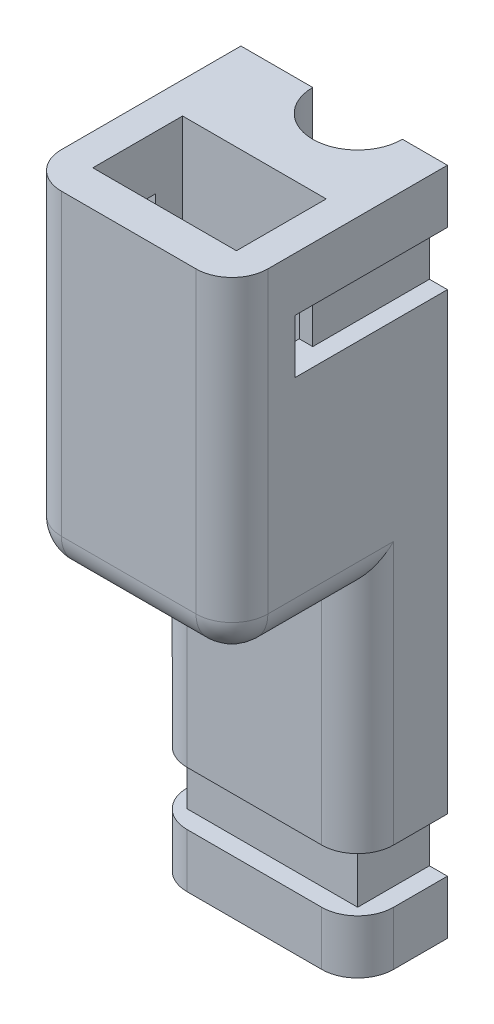
SolidWorks part; units mm, degrees
ref_plane "Alzado" through (0, 0, 0) normal (0, 0, 1) x (1, 0, 0)
ref_plane "Planta" through (0, 0, 0) normal (0, 1, 0) x (1, 0, 0)
ref_plane "Vista lateral" through (0, 0, 0) normal (1, 0, 0) x (0, 0, -1)
sketch "Croquis1" plane through (0, 0, 0) normal (0, 0, 1) x (1, 0, 0)
  line L0 (0, 7) -> (0, -7)
  line L1 (0, -7) -> (0, -10)
  line L2 (0, 0) -> (-3.5, 0) construction
  line L3 (-3.5, 7) -> (-3.5, -7)
  line L4 (-3.5, -7) -> (-2.5, -9.6451)
  line L5 (-2.5, -9.6451) -> (-2.5, -18.6451)
  line L6 (-2.5, -18.6451) -> (-0.8, -18.6451)
  line L12 (0, 7) -> (0, 10)
  line L18 (-2.5, 18.6451) -> (-0.8, 18.6451)
  line L19 (-2.5, 9.6451) -> (-2.5, 18.6451)
  line L20 (-3.5, 7) -> (-2.5, 9.6451)
  dimension "D1" = 7
  dimension "D2" = 3
  dimension "D3" = 7
  dimension "D4" = 9
  dimension "D5" = 2.5
  dimension "D6" = 3.5
  dimension "D7" = 1.7
ref_plane "Plano1" through (0, 0, 0) normal (0, 0, 1) x (1, 0, 0)
sketch "Croquis2" plane through (0, 0, 0) normal (0, 0, 1) x (1, 0, 0)
  line L0 (0, 18.6451) -> (-2.5, 18.6451)
  line L1 (-2.5, 18.6451) -> (-2.5, 9.6451)
  line L2 (-2.5, 9.6451) -> (-3.5, 7)
  line L3 (-3.5, 7) -> (-3.5, -7)
  line L4 (-3.5, -7) -> (-2.5, -9.6451)
  line L5 (-2.5, -9.6451) -> (-2.5, -18.6451)
  line L6 (-2.5, -18.6451) -> (0, -18.6451)
  line L7 (0, -18.6451) -> (0, 18.6451)
  line L9 (-6.5, 18.6451) -> (5, 18.6451)
  line L10 (-6.5, 18.6451) -> (-6.5, -18.6451)
  line L11 (-6.5, -18.6451) -> (5, -18.6451)
  line L12 (5, 18.6451) -> (5, -18.6451)
  dimension "D1" = 5
  dimension "D2" = 3
extrude "Saliente-Extruir1" add sketch "Croquis2" along normal blind 5 contours L12 L11 L10 L9
revolve "Cortar-Revolución1" cut sketch "Croquis2<4>" angle 360 about L12 region at (-1.5111, 0, 0)
sketch "Croquis2<4>" plane through (0, 0, 0) normal (0, 0, 1) x (1, 0, 0) same geometry as "Croquis2"
sketch "Croquis3" plane through (0, 0, 0) normal (0, 0, -1) x (-1, 0, 0)
  line L0 (0, 0) -> (0, 3.5)
  line L1 (0, 7) -> (0, -7) construction
  line L5 (12, 2.5) -> (0, 3.5)
  line L6 (12, 0) -> (12, 2.5)
  line L7 (0, 0) -> (12, 0)
  dimension "D1" = 3.5
revolve "Cortar-Revolución2" cut sketch "Croquis3" angle 360 about L7
sketch "Croquis6" plane through (0, 0, 5) normal (0, 0, 1) x (1, 0, 0)
  line L0 (5, 18.6451) -> (5, -18.6451) construction
  line L1 (5, 0) -> (-6.5, 0)
  line L2 (5, 0) -> (5, 18.6451)
  line L3 (5, 18.6451) -> (-6.5, 18.6451)
  line L4 (-6.5, 0) -> (-6.5, 18.6451)
extrude "Saliente-Extruir2" add sketch "Croquis6" along normal blind 7
sketch "Croquis4" plane through (0, 0, 0) normal (0, 0, -1) x (-1, 0, 0)
  line L0 (-5, 18.6451) -> (-5, -18.6451) construction
  line L1 (-5, 15.6451) -> (-4, 15.6451)
  line L2 (-5, 15.6451) -> (-5, 12.6451)
  line L3 (-5, 12.6451) -> (-4, 12.6451)
  line L4 (-4, 15.6451) -> (-4, 12.6451)
  line L5 (-2.5, 18.6451) -> (-5, 18.6451) construction
  line L6 (5.5, 15.6451) -> (6.5, 15.6451)
  line L7 (5.5, 15.6451) -> (5.5, 12.6451)
  line L8 (5.5, 12.6451) -> (6.5, 12.6451)
  line L9 (6.5, 15.6451) -> (6.5, 12.6451)
  line L10 (5.5, -12.6451) -> (6.5, -12.6451)
  line L11 (5.5, -12.6451) -> (5.5, -15.6451)
  line L12 (5.5, -15.6451) -> (6.5, -15.6451)
  line L13 (6.5, -12.6451) -> (6.5, -15.6451)
  line L14 (-5, -12.6451) -> (-4, -12.6451)
  line L15 (-5, -12.6451) -> (-5, -15.6451)
  line L16 (-5, -15.6451) -> (-4, -15.6451)
  line L17 (-4, -12.6451) -> (-4, -15.6451)
  line L18 (-2.5, -18.6451) -> (-5, -18.6451) construction
  line L19 (6.5, 18.6451) -> (6.5, 2.9583) construction
  dimension "D1" = 1
  dimension "D2" = 3
  dimension "D3" = 3
  dimension "D6" = 3
  dimension "D7" = 0
  dimension "D4" = 2
  dimension "D5" = 2
extrude "Cortar-Extruir2" cut sketch "Croquis4" against normal blind 6.5
sketch "Croquis5" plane through (4, 0, 0) normal (1, 0, 0) x (0, 0, -1)
  line L0 (-6.5, 15.6451) -> (0, 15.6451) construction
  line L1 (-8.5, 12.6451) -> (-6.5, 12.6451)
  line L2 (-8.5, 12.6451) -> (-8.5, 15.6451)
  line L3 (-8.5, 15.6451) -> (-6.5, 15.6451)
  line L4 (-6.5, 12.6451) -> (-6.5, 15.6451)
  line L5 (-5, -15.6451) -> (-5, -12.6451) construction
  line L6 (-7.9583, -12.6451) -> (-7.9583, -15.6451)
  line L7 (-4, -15.6451) -> (-7.9583, -15.6451)
  line L8 (-4, -12.6451) -> (-4, -15.6451)
  line L9 (-4, -12.6451) -> (-7.9583, -12.6451)
  line L10 (0, 12.6451) -> (0, 15.6451) construction
  dimension "D1" = 2
  dimension "D2" = 6.5
  dimension "D3" = 1
extrude "Cortar-Extruir3" cut sketch "Croquis5" against normal up to vertex (10.5 mm away) and the other way up to vertex (1 mm away) up to point (-6.5, 18.6451, 12) other way up to point (5, 18.6451, 12)
sketch "Croquis7" plane through (0, 18.6451, 0) normal (0, 1, 0) x (1, 0, 0)
  line L0 (5, -12) -> (-6.5, -12) construction
  line L1 (3.25, -10) -> (-4.75, -10)
  line L2 (3.25, -10) -> (3.25, -5)
  line L3 (3.25, -5) -> (-4.75, -5)
  line L4 (-4.75, -10) -> (-4.75, -5)
  line L5 (-6.5, -12) -> (-6.5, 0) construction
  dimension "D1" = 8
  dimension "D2" = 5
  dimension "D3" = 2
  dimension "D4" = 1.75
extrude "Cortar-Extruir4" cut sketch "Croquis7" against normal blind 15
fillet "Redondeo1" radius 2 9 edges at (5, 0, 8.5) (-6.5, 0, 8.5) (-0.75, 0, 12) (5, 9.3225, 12) (-6.5, 9.3225, 12) (5, -17.1451, 5) (-6.5, -17.1451, 5) (5, -6.3225, 5) (-6.5, -6.3225, 5)
